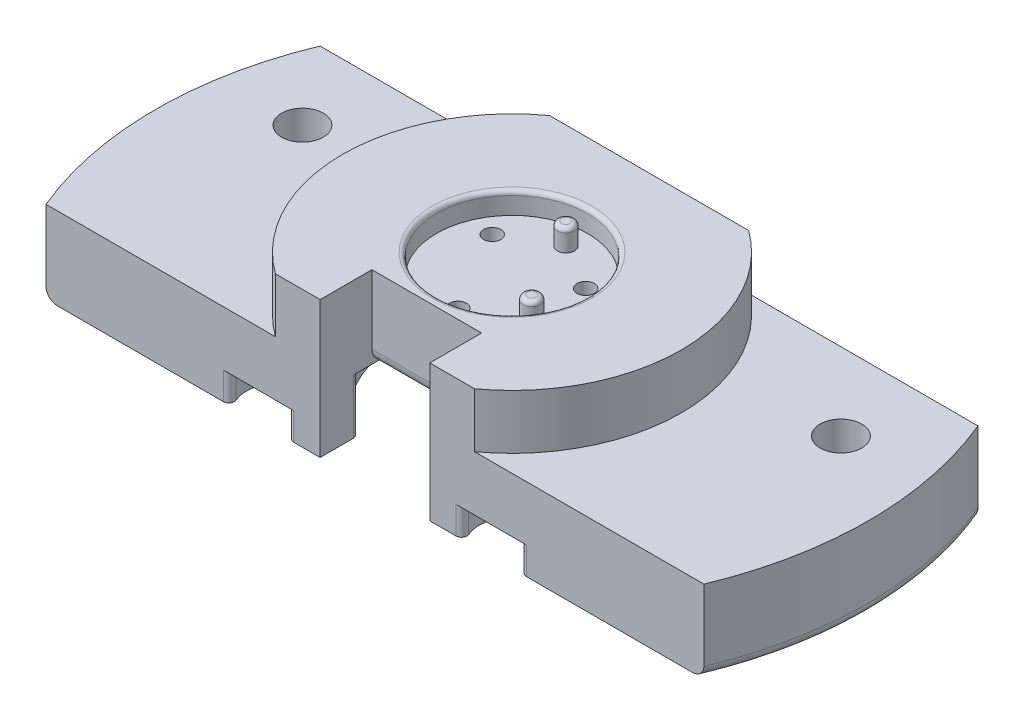
SolidWorks part; units mm, degrees
material "ABS"
ref_plane "Front Plane" through (0, 0, 0) normal (0, 0, 1) x (1, 0, 0)
ref_plane "Top Plane" through (0, 0, 0) normal (0, 1, 0) x (1, 0, 0)
ref_plane "Right Plane" through (0, 0, 0) normal (1, 0, 0) x (0, 0, -1)
sketch "Sketch1" plane through (0, 0, 0) normal (0, 0, 1) x (1, 0, 0)
  line L0 (0, 52.8436) -> (0, -40.6212) construction
  line L1 (0, 63.5) -> (41.275, 63.5)
  line L2 (41.275, 63.5) -> (41.275, 0)
  line L3 (41.275, 0) -> (13.2715, 0)
  line L4 (13.2715, 0) -> (13.2715, 6.35)
  line L5 (13.2715, 6.35) -> (10.0965, 6.35)
  line L6 (10.0965, 6.35) -> (10.0965, -57.15)
  line L7 (10.0965, -57.15) -> (0, -57.15)
  line L8 (0, -57.15) -> (0, 63.5)
  dimension "D1" = 57.15
  dimension "D2" = 20.193
  dimension "D3" = 6.35
  dimension "D4" = 3.175
  dimension "D7" = 82.55
  dimension "D8" = 63.5
revolve "Revolve1" add sketch "Sketch1" angle 360 about L0 region at (17.8637, 20.9777, 0)
sketch "Sketch30" plane through (0, 0, 0) normal (0, -1, 0) x (1, 0, 0)
  line L0 (-41.275, 0) -> (41.275, 0) construction
  line L1 (-41.275, -25.4) -> (41.275, -25.4)
  line L2 (-41.275, -25.4) -> (-41.275, 25.4)
  line L3 (-41.275, 25.4) -> (41.275, 25.4)
  line L4 (41.275, -25.4) -> (41.275, 25.4)
  circle A0 centre (0, 0) radius 41.275 construction
  point P4 (-41.275, 0)
  point P6 (41.275, 0)
  dimension "D1" = 25.4
  dimension "D2" = 25.4
extrude "Cut-Extrude21" cut sketch "Sketch30" against normal through all flip side to cut
shell "Shell1" thickness 6.35 removed face at (0, 63.5, 0)
sketch "Sketch18" plane through (0, 63.5, 0) normal (0, 1, 0) x (1, 0, 0)
  line L0 (-53.0132, 0) -> (55.6586, 0) construction
  line L1 (-31.75, 14.5497) -> (-31.75, -14.5497)
  line L2 (0, 40.7916) -> (0, -40.1567) construction
  line L3 (31.75, 14.5497) -> (31.75, -14.5497)
  arc A1 (31.75, -14.5497) -> (31.75, 14.5497) centre (0, 0) ccw
  circle A2 centre (0, 0) radius 34.925 construction
  arc A3 (-31.75, 14.5497) -> (-31.75, -14.5497) centre (0, 0) ccw
  dimension "D1" = 63.5
extrude "Boss-Extrude1" add sketch "Sketch18" against normal up to next
sketch "Sketch19" plane through (0, 0, 0) normal (1, 0, 0) x (0, 0, -1)
  circle A0 centre (-33.02, 12.7) radius 4.7625 construction
  circle A1 centre (-9.6347, 31.75) radius 25.4 construction
  circle A2 centre (-9.6347, 31.75) radius 3.175
  point P5 (-9.6347, 6.35)
  dimension "D1" = 9.525
  dimension "D4" = 6.35
  dimension "D5" = 50.8
  dimension "D2" = 33.02
  dimension "D3" = 12.7
  dimension "D6" = 6.35
extrude "Cut-Extrude12" cut sketch "Sketch19" against normal through all and the other way through all
ref_plane "Plane1" through (26.9875, 0, 0) normal (1, 0, 0) x (0, 0, -1)
sketch "Sketch21" plane through (26.9875, 0, 0) normal (1, 0, 0) x (0, 0, -1)
  circle A1 centre (-9.6347, 31.75) radius 3.175 construction
  circle A2 centre (-9.6347, 31.75) radius 28.2575
  dimension "D1" = 56.515
extrude "Cut-Extrude13" cut sketch "Sketch21" against normal blind 4.7625 and the other way blind 4.7625
ref_plane "Plane3" through (23.495, 0, 0) normal (1, 0, 0) x (0, 0, -1)
sketch "Sketch22" plane through (23.495, 0, 0) normal (1, 0, 0) x (0, 0, -1)
  circle A0 centre (-9.6347, 31.75) radius 17.78
  dimension "D1" = 35.56
extrude "Cut-Extrude15" cut sketch "Sketch22" against normal blind 5.08 and the other way blind 5.08
mirror "Mirror1" about plane through (0, 0, 0) normal (1, 0, 0) of "Cut-Extrude15"
ref_plane "Plane2" through (-23.495, 0, 0) normal (1, 0, 0) x (0, 0, -1)
ref_plane "Plane4" through (-16.8275, 0, 0) normal (1, 0, 0) x (0, 0, -1)
sketch "Sketch23" plane through (-16.8275, 0, 0) normal (-1, 0, 0) x (0, 0, 1)
  circle A1 centre (9.6347, 31.75) radius 13.97
  dimension "D1" = 27.94
extrude "Cut-Extrude16" cut sketch "Sketch23" against normal blind 4.7625 and the other way blind 4.7625
sketch "Sketch24" plane through (0, 12.7, 0) normal (0, 1, 0) x (1, 0, 0)
  circle A0 centre (0, 0) radius 3.7465 construction
  circle A1 centre (0, 0) radius 3.7465
extrude "Cut-Extrude17" cut sketch "Sketch24" against normal through all and the other way through all
sketch "Sketch25" plane through (0, -57.15, 0) normal (0, -1, 0) x (1, 0, 0)
  circle A0 centre (0, 0) radius 3.7465
  circle A2 centre (0, 0) radius 3.7465 construction
extrude "Boss-Extrude2" add sketch "Sketch25" against normal offset from surface (66.04 mm away) 3.81 up to face at (0, 12.7, -3.7465)
sketch "Sketch26" plane through (0, 0, 0) normal (0, 0, 1) x (1, 0, 0)
  line L0 (0, 63.5) -> (0, 0) construction
  line L1 (41.275, 63.5) -> (-41.275, 63.5) construction
  line L2 (-6.4135, 76.2) -> (-12.7, 76.2)
  line L4 (0, 63.5) -> (0, 76.2) construction
  line L5 (-6.4135, 76.2) -> (-6.4135, 63.5)
  line L6 (-41.275, 63.5) -> (-41.275, 69.85)
  line L7 (-41.275, 69.85) -> (-6.4135, 69.85) construction
  line L9 (-41.275, 63.5) -> (-6.4135, 63.5)
  arc A0 (-41.275, 69.85) -> (-12.7, 76.2) centre (-41.275, 137.3188) ccw
  point P7 (-41.275, 63.5)
  dimension "D1" = 12.7
  dimension "D2" = 6.35
  dimension "D4" = 12.827
  dimension "D6" = 6.35
revolve "Revolve2" add sketch "Sketch26" angle 360 about L0
sketch "Sketch31" plane through (0, 63.5, 0) normal (0, -1, 0) x (1, 0, 0)
  line L0 (32.5341, -25.4) -> (-32.5341, -25.4) construction
  line L1 (-32.5341, 25.4) -> (32.5341, 25.4) construction
  line L2 (32.5341, -25.4) -> (-32.5341, -25.4)
  line L3 (-32.5341, 25.4) -> (32.5341, 25.4)
  arc A0 (-32.5341, -25.4) -> (32.5341, -25.4) centre (0, 0) ccw construction
  arc A1 (32.5341, 25.4) -> (-32.5341, 25.4) centre (0, 0) ccw construction
  arc A2 (-32.5341, -25.4) -> (32.5341, -25.4) centre (0, 0) ccw
  arc A3 (32.5341, 25.4) -> (-32.5341, 25.4) centre (0, 0) ccw
extrude "Cut-Extrude22" cut sketch "Sketch31" against normal through all
sketch "Sketch32" plane through (0, 0, 0) normal (0, 1, 0) x (1, 0, 0)
  line L1 (-44.6628, 69.85) -> (50.6238, 69.85)
  line L2 (-44.6628, 69.85) -> (-44.6628, 19.05)
  line L3 (-44.6628, 19.05) -> (50.6238, 19.05)
  line L4 (50.6238, 69.85) -> (50.6238, 19.05)
  dimension "D1" = 19.05
  dimension "D2" = 50.8
extrude "Cut-Extrude23" cut sketch "Sketch32" against normal through all and the other way through all
sketch "Sketch37" plane through (0, 76.2, 0) normal (0, 1, 0) x (1, 0, 0)
  line L0 (-8.7312, 0) -> (8.7312, 0) construction
  circle A0 centre (-8.7312, 0) radius 0.889
  circle A1 centre (8.7312, 0) radius 0.889
  point P2 (0, 0)
  dimension "D2" = 1.778
  dimension "D1" = 17.4625
extrude "Cut-Extrude27" cut sketch "Sketch37" against normal up to surface (12.7 mm away) up to face at (0, 63.5, 6.4135)
sketch "Sketch39" plane through (0, 0, 0) normal (0, -1, 0) x (1, 0, 0)
  circle A0 centre (-19.05, 0) radius 3.175 construction
  circle A1 centre (19.05, 0) radius 3.175 construction
  circle A2 centre (-19.05, 0) radius 3.175 construction
  circle A3 centre (19.05, 0) radius 3.175 construction
  circle A4 centre (-19.05, 0) radius 3.1242
  circle A5 centre (19.05, 0) radius 3.1242
  dimension "D1" = 0.0508
extrude "Boss-Extrude3" add sketch "Sketch39" along normal blind 2.54
fillet "Fillet1" radius 0.635 2 edges at (19.05, -2.54, -3.1242) (-19.05, -2.54, -3.1242)
sketch "Sketch40" plane through (0, 0, 0) normal (0, -1, 0) x (1, 0, 0)
  circle A0 centre (-31.1852, -6.9148) radius 1.778 construction
  circle A1 centre (31.1852, -6.9148) radius 1.778 construction
  circle A2 centre (-31.1852, -6.9148) radius 1.778 construction
  circle A3 centre (31.1852, -6.9148) radius 1.778 construction
  circle A4 centre (31.1852, -6.9148) radius 1.905
  circle A5 centre (-31.1852, -6.9148) radius 1.905
  dimension "D1" = 3.81
extrude "Cut-Extrude28" cut sketch "Sketch40" against normal blind 6.35
sketch "Sketch41" plane through (0, 76.2, 0) normal (0, 1, 0) x (1, 0, 0)
  circle A0 centre (0, 0) radius 11.303
  dimension "D1" = 22.606
extrude "Cut-Extrude29" cut sketch "Sketch41" against normal blind 6.35
sketch "Sketch43" plane through (0, 6.35, 0) normal (0, 1, 0) x (1, 0, 0)
  line L0 (-31.75, 19.05) -> (-31.75, -25.4)
  line L2 (-32.5341, -25.4) -> (32.5341, -25.4) construction
  line L3 (31.75, -25.4) -> (31.75, 19.05)
  line L4 (-31.75, -14.5497) -> (-31.75, 5.0954) construction
  line L5 (36.6159, 19.05) -> (-36.6159, 19.05) construction
  line L6 (31.75, 5.0954) -> (31.75, 2.7478) construction
  line L7 (-31.75, 19.05) -> (-4.7011, 19.05)
  line L8 (4.7011, 19.05) -> (31.75, 19.05)
  line L9 (-31.75, -25.4) -> (31.75, -25.4)
  arc A0 (-4.7011, 19.05) -> (4.7011, 19.05) centre (0, 0) ccw
  arc A1 (-4.7011, 19.05) -> (-4.7011, -19.05) centre (0, 0) ccw construction
extrude "Cut-Extrude31" cut sketch "Sketch43" along normal up to surface (57.15 mm away) up to face at (8.7312, 63.5, -0.889)
sketch "Sketch44" plane through (0, 12.7, 0) normal (0, 1, 0) x (1, 0, 0)
  circle A0 centre (0, 0) radius 19.6215
  arc A2 (4.7011, -19.05) -> (4.7011, 19.05) centre (0, 0) ccw construction
extrude "Cut-Extrude32" cut sketch "Sketch44" along normal up to surface (50.8 mm away)
ref_plane "Plane5" through (33.9725, 0, 0) normal (1, 0, 0) x (0, 0, -1)
sketch "Sketch45" plane through (33.9725, 0, 0) normal (1, 0, 0) x (0, 0, -1)
  line L0 (-9.6347, 45.339) -> (-9.6347, 37.719) construction
  circle A0 centre (-9.6347, 31.75) radius 9.779 construction
  circle A1 centre (-9.6347, 31.75) radius 5.969
  circle A2 centre (-9.6347, 31.75) radius 13.589
  point P7 (-9.6347, 41.529)
  dimension "D1" = 19.558
  dimension "D2" = 7.62
extrude "Cut-Extrude33" cut sketch "Sketch45" against normal up to surface (2.2225 mm away) up to face at (31.75, 20.2803, 2.2675)
sketch "Sketch48" plane through (0, 6.35, 0) normal (0, -1, 0) x (1, 0, 0)
  circle A0 centre (0, 0) radius 13.2715
  circle A1 centre (0, 0) radius 13.2715 construction
extrude "Cut-Extrude35" cut sketch "Sketch48" along normal through all
sketch "Sketch49" plane through (0, 0, 0) normal (0, -1, 0) x (1, 0, 0)
  line L1 (50.8, -15.875) -> (-50.8, -15.875)
  line L2 (50.8, -15.875) -> (50.8, 15.875)
  line L3 (50.8, 15.875) -> (-50.8, 15.875)
  line L4 (-50.8, -15.875) -> (-50.8, 15.875)
  line L5 (50.8, -15.875) -> (-50.8, 15.875) construction
  line L6 (50.8, 15.875) -> (-50.8, -15.875) construction
  point P0 (0, 0)
  dimension "D1" = 101.6
  dimension "D2" = 31.75
extrude "Cut-Extrude36" cut sketch "Sketch49" against normal through all flip side to cut
sketch "Sketch50" plane through (0, 0, 0) normal (0, -1, 0) x (1, 0, 0)
  line L1 (13.4704, -13.4704) -> (-13.4704, -13.4704) construction
  line L2 (13.4704, -13.4704) -> (13.4704, 13.4704) construction
  line L3 (13.4704, 13.4704) -> (-13.4704, 13.4704) construction
  line L4 (-13.4704, -13.4704) -> (-13.4704, 13.4704) construction
  line L5 (13.4704, -13.4704) -> (-13.4704, 13.4704) construction
  line L6 (13.4704, 13.4704) -> (-13.4704, -13.4704) construction
  circle A0 centre (-13.4704, 13.4704) radius 3.81
  circle A1 centre (13.4704, 13.4704) radius 3.81
  circle A2 centre (13.4704, -13.4704) radius 3.81
  circle A3 centre (-13.4704, -13.4704) radius 3.81
  point P0 (0, 0)
  dimension "D2" = 7.62
  dimension "D1" = 38.1
extrude "Cut-Extrude37" cut sketch "Sketch50" against normal blind 3.175
fillet "Fillet2" radius 0.635 10 edges at (16.4257, 1.5875, 15.875) (10.5151, 1.5875, 15.875) (-10.5151, 1.5875, 15.875) (-16.4257, 1.5875, 15.875) (16.4257, 1.5875, -15.875) (-10.5151, 1.5875, -15.875) (10.5151, 1.5875, -15.875) (-16.4257, 1.5875, -15.875) (32.8613, 43.8214, 15.875) (32.8613, 19.6786, 15.875)
fillet "Fillet3" radius 1.27 4 edges at (41.275, 0, 0) (-41.275, 0, 0) (-41.275, 69.85, 0) (41.275, 69.85, 0)
sketch "Sketch51" plane through (0, 0, 0) normal (1, 0, 0) x (0, 0, -1)
  line L0 (-15.875, 9.525) -> (-9.875, 9.525)
  line L1 (-15.875, 68.5917) -> (-15.875, 1.27) construction
  line L2 (-9.875, 9.525) -> (-9.875, 0)
  line L3 (-3.1242, 0) -> (3.1242, 0) construction
  line L4 (-9.875, 0) -> (-15.875, 0)
  line L5 (-15.875, 0) -> (-15.875, 9.525)
  dimension "D2" = 9.525
  dimension "D3" = 6
extrude "Cut-Extrude38" cut sketch "Sketch51" against normal blind 6.35 and the other way blind 6.35
fillet "Fillet4" radius 0.635 2 edges at (6.35, 3.175, 11.6538) (-6.35, 3.175, 11.6538)
sketch "Sketch52" plane through (0, 9.525, 0) normal (0, -1, 0) x (1, 0, 0)
  line L0 (-6.35, 9.875) -> (-6.35, 15.875) construction
  line L1 (6.35, 15.875) -> (-6.35, 15.875)
  line L2 (6.35, 15.875) -> (6.35, 9.875)
  line L3 (6.35, 9.875) -> (-6.35, 9.875)
  line L4 (-6.35, 15.875) -> (-6.35, 9.875)
  dimension "D1" = 6
extrude "Cut-Extrude39" cut sketch "Sketch52" against normal up to next
sketch "Sketch59" plane through (0, 12.7, 0) normal (0, 1, 0) x (1, 0, 0)
  circle A0 centre (0, 0) radius 3.7465
  circle A1 centre (0, 0) radius 3.7465 construction
extrude "Boss-Extrude6" add sketch "Sketch59" against normal up to surface (3.81 mm away) up to face at (0, 8.89, -3.7465)
sketch "Sketch53" plane through (0, 0, 0) normal (0, 0, 1) x (1, 0, 0)
  line L0 (-19.6215, 6.35) -> (-19.6215, 12.7)
  line L1 (-19.6215, 6.35) -> (-19.6215, 12.7)
  line L2 (0, 88.9) -> (0, 12.7)
  line L4 (-19.6215, 12.7) -> (0, 12.7)
  line L7 (0, 88.9) -> (-45.0215, 88.9)
  line L8 (-45.0215, 88.9) -> (-45.0215, 6.35)
  line L9 (-45.0215, 6.35) -> (-19.6215, 6.35)
  line L10 (0, 100.3738) -> (0, -20.5217) construction
  dimension "D1" = 76.2
  dimension "D2" = 25.4
revolve "Cut-Revolve1" cut sketch "Sketch53" angle 360 about L10
sketch "Sketch54" plane through (0, 6.35, 0) normal (0, 1, 0) x (1, 0, 0)
  line L0 (22.225, -15.875) -> (11.532, -15.875) construction
  line L1 (20.955, -15.875) -> (34.29, -15.875)
  line L2 (20.955, -15.875) -> (20.955, 4.0178)
  line L3 (20.955, 4.0178) -> (34.29, 4.0178)
  line L4 (34.29, -15.875) -> (34.29, 4.0178)
  line L5 (31.75, 2.7478) -> (31.75, -15.875) construction
  line L6 (22.225, 2.7478) -> (22.225, -15.875) construction
  line L7 (31.75, 2.7478) -> (22.225, 2.7478) construction
  dimension "D1" = 2.54
  dimension "D2" = 1.27
  dimension "D3" = 1.27
extrude "Boss-Extrude4" add sketch "Sketch54" against normal up to body
sketch "Sketch62" plane through (0, 6.35, 0) normal (0, 1, 0) x (1, 0, 0)
  line L0 (-38.1, -15.875) -> (-11.532, -15.875) construction
  line L1 (-11.532, 15.875) -> (-38.1, 15.875) construction
  line L2 (11.532, -15.875) -> (38.1, -15.875) construction
  line L3 (38.1, 15.875) -> (11.532, 15.875) construction
  line L4 (-38.1, -15.875) -> (-11.532, -15.875)
  line L5 (-11.532, 15.875) -> (-38.1, 15.875)
  line L6 (11.532, -15.875) -> (38.1, -15.875)
  line L7 (38.1, 15.875) -> (11.532, 15.875)
  arc A0 (-11.532, 15.875) -> (-11.532, -15.875) centre (0, 0) ccw construction
  arc A1 (-38.1, 15.875) -> (-38.1, -15.875) centre (0, 0) ccw construction
  arc A2 (38.1, -15.875) -> (38.1, 15.875) centre (0, 0) ccw construction
  arc A3 (11.532, -15.875) -> (11.532, 15.875) centre (0, 0) ccw construction
  arc A4 (-11.532, 15.875) -> (-11.532, -15.875) centre (0, 0) ccw
  arc A5 (-38.1, 15.875) -> (-38.1, -15.875) centre (0, 0) ccw
  arc A6 (38.1, -15.875) -> (38.1, 15.875) centre (0, 0) ccw
  arc A7 (11.532, -15.875) -> (11.532, 15.875) centre (0, 0) ccw
  circle A8 centre (-31.1852, 6.9148) radius 1.905 construction
  circle A9 centre (31.1852, 6.9148) radius 1.905 construction
  circle A10 centre (-31.1852, 6.9148) radius 1.905
  circle A11 centre (31.1852, 6.9148) radius 1.905
extrude "Boss-Extrude7" add sketch "Sketch62" along normal blind 3.175
sketch "Sketch63" plane through (0, 9.525, 0) normal (0, 1, 0) x (1, 0, 0)
  circle A0 centre (31.1852, 6.9148) radius 2.413
  circle A1 centre (-31.1852, 6.9148) radius 2.413
  dimension "D1" = 4.826
extrude "Cut-Extrude45" cut sketch "Sketch63" against normal blind 6.35
sketch "Sketch69" plane through (0, 12.7, 0) normal (0, 1, 0) x (1, 0, 0)
  line L0 (-6.35, -15.875) -> (-11.532, -15.875) construction
  line L1 (-6.35, -9.875) -> (-6.35, -15.875) construction
  line L2 (6.35, -9.875) -> (-6.35, -9.875) construction
  line L3 (6.35, -15.875) -> (6.35, -9.875) construction
  line L4 (11.532, -15.875) -> (6.35, -15.875) construction
  line L5 (-11.532, 15.875) -> (11.532, 15.875) construction
  line L6 (-6.35, -15.875) -> (-11.532, -15.875)
  line L7 (-6.35, -9.875) -> (-6.35, -15.875)
  line L8 (6.35, -9.875) -> (-6.35, -9.875)
  line L9 (6.35, -15.875) -> (6.35, -9.875)
  line L10 (11.532, -15.875) -> (6.35, -15.875)
  line L11 (-11.532, 15.875) -> (11.532, 15.875)
  arc A0 (-11.532, 15.875) -> (-11.532, -15.875) centre (0, 0) ccw construction
  arc A1 (11.532, -15.875) -> (11.532, 15.875) centre (0, 0) ccw construction
  arc A2 (-11.532, 15.875) -> (-11.532, -15.875) centre (0, 0) ccw
  arc A3 (11.532, -15.875) -> (11.532, 15.875) centre (0, 0) ccw
extrude "Boss-Extrude9" add sketch "Sketch69" along normal blind 3.14
fillet "Fillet7" radius 1.5 1 edges at (0, 6.35, 9.875)
sketch "Sketch70" plane through (0, 15.84, 0) normal (0, 1, 0) x (1, 0, 0)
  circle A0 centre (0, 0) radius 8.75
extrude "Cut-Extrude46" cut sketch "Sketch70" against normal blind 2.5
sketch "Sketch71" plane through (0, 13.34, 0) normal (0, 1, 0) x (1, 0, 0)
  line L0 (0, 0) -> (0, 6.25) construction
  circle A0 centre (0, 0) radius 6.25 construction
  circle A1 centre (0, 6.25) radius 1
  circle A2 centre (5.4127, -3.125) radius 1
  circle A4 centre (-5.4127, -3.125) radius 1 [skipped]
  point P11 (0, 0)
  dimension "D1" = 3
extrude "Boss-Extrude10" add sketch "Sketch71" along normal blind 2.5
sketch "Sketch72" plane through (0, 13.34, 0) normal (0, 1, 0) x (1, 0, 0)
  line L0 (0, 0) -> (0, -6.25) construction
  circle A0 centre (0, 0) radius 6.25 construction
  circle A1 centre (0, -6.25) radius 1
  circle A2 centre (-5.4127, 3.125) radius 1
  circle A3 centre (5.4127, 3.125) radius 1
  point P11 (0, 0)
  dimension "D1" = 3
extrude "Cut-Extrude47" cut sketch "Sketch72" against normal through all
fillet "Fillet8" radius 0.5 3 edges at (0, 15.84, 8.75) (5.4127, 15.84, 4.125) (0, 15.84, -5.25)
